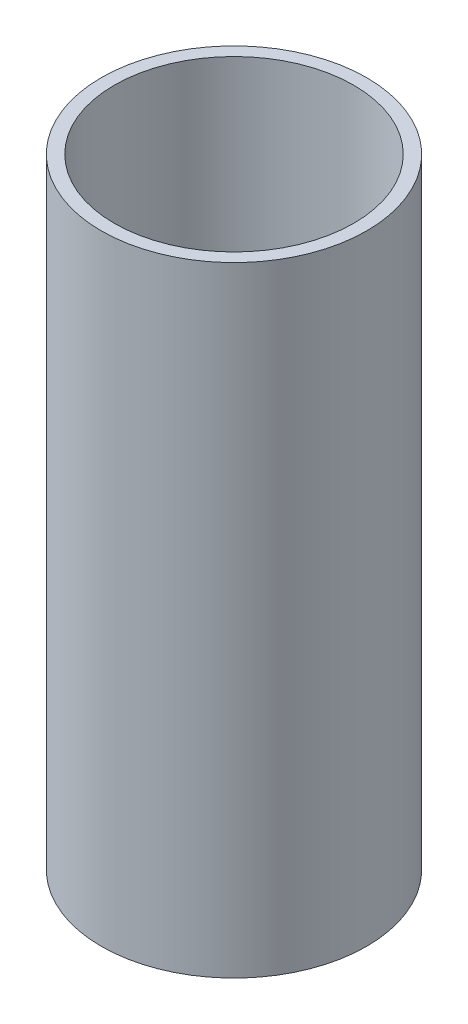
SolidWorks part; units mm, degrees
ref_plane "Front Plane" through (0, 0, 0) normal (0, 0, 1) x (1, 0, 0)
ref_plane "Top Plane" through (0, 0, 0) normal (0, 1, 0) x (1, 0, 0)
ref_plane "Right Plane" through (0, 0, 0) normal (1, 0, 0) x (0, 0, -1)
sketch "Sketch1" plane through (0, 0, 0) normal (0, 1, 0) x (1, 0, 0)
  circle A0 centre (0, 0) radius 42.5
  dimension "SLEEVE_OD" = 85
extrude "Boss-Extrude1" add sketch "Sketch1" along normal blind 198.4368
sketch "Sketch2" plane through (0, 0, 0) normal (0, 1, 0) x (1, 0, 0)
  circle A0 centre (0, 0) radius 38.3351
  dimension "BORE_D" = 76.6701
extrude "Cut-Extrude1" cut sketch "Sketch2" along normal through all
chamfer "Chamfer1" distance 3.4167 angle 30 rebuild error yes
